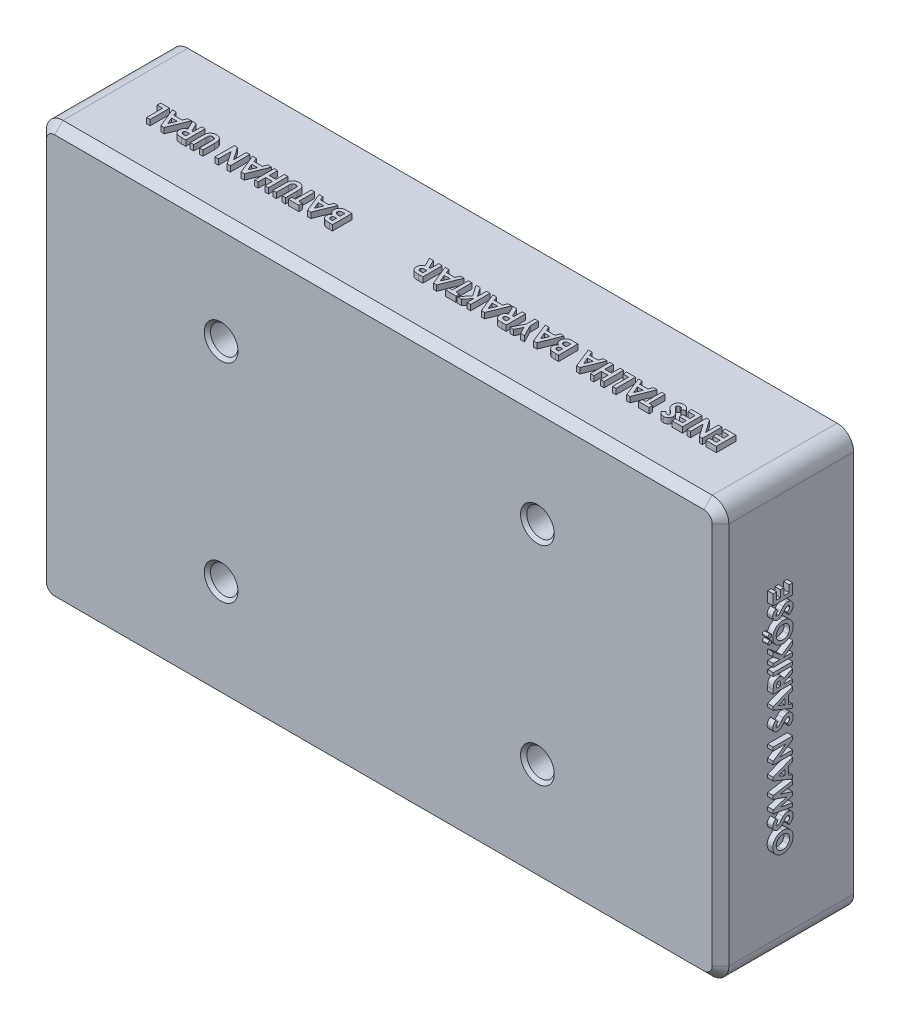
SolidWorks part; units mm, degrees
ref_plane "Ön Düzlem" through (0, 0, 0) normal (0, 0, 1) x (1, 0, 0)
ref_plane "Üst Düzlem" through (0, 0, 0) normal (0, 1, 0) x (1, 0, 0)
ref_plane "Sağ Düzlem" through (0, 0, 0) normal (1, 0, 0) x (0, 0, -1)
sketch "Sketch1" plane through (0, 0, 0) normal (0, 0, 1) x (1, 0, 0)
  line L5 (0, 0) -> (-82, 0)
  line L6 (0, 0) -> (0, 50)
  line L7 (0, 50) -> (-82, 50)
  line L8 (-82, 0) -> (-82, 50)
  dimension "D1" = 82
  dimension "D2" = 50
extrude "Boss-Extrude4" add sketch "Sketch1" along normal blind 16
hole_wizard "M4 Tapped Hole1" positions "Sketch3" profile "Sketch4" tap size "M4" standard "DIN"
sketch "Sketch3" plane through (0, 0, 16) normal (0, 0, 1) x (1, 0, 0)
  line L1 (-41, 50) -> (-41, 0) construction
  line L2 (0, 50) -> (-82, 50) construction
  line L3 (-82, 0) -> (0, 0) construction
  line L6 (-82, 25) -> (0, 25) construction
  line L7 (-82, 50) -> (-82, 0) construction
  line L8 (0, 0) -> (0, 50) construction
  point P0 (-60, 37.5)
  point P2 (-60, 12.5)
  point P4 (-22, 12.5)
  point P6 (-22, 37.5)
  dimension "D1" = 38
  dimension "D2" = 25
sketch "Sketch4" plane through (-60, 37.5, 16) normal (1, 0, 0) x (0, -1, 0)
  line L0 (0, 0) -> (0, 8.9914)
  line L1 (0, 8.9914) -> (1.65, 8)
  line L2 (1.65, 8) -> (1.65, 0.375)
  line L3 (1.65, 0.375) -> (2.025, 0)
  line L5 (2.025, 0) -> (0, 0)
  line L6 (-1.65, 0.375) -> (-2.025, 0) construction
  line L10 (0, 8.9914) -> (-1.65, 8) construction
  line L11 (0, -6.35) -> (0, 107.95) construction
  dimension "Tap Drill Dia." = 3.3
  dimension "Tap Drill Depth" = 8
  dimension "Near C'Sink Dia." = 4.05
  dimension "Near C'Sink Angle" = 90
  dimension "Drill Angle" = 118
cosmetic thread "Hole Thread1" parameters "D1"=6, "D2"=4
cosmetic thread "Hole Thread2" parameters "D1"=6, "D2"=4
cosmetic thread "Hole Thread3" parameters "D1"=6, "D2"=4
cosmetic thread "Hole Thread4" parameters "D1"=6, "D2"=4
scale "Scale1" scale about centroid uniform scaling yes scale factor 1.5
sketch "Sketch5" plane through (0, -12.5, 0) normal (0, -1, 0) x (1, 0, 0)
  line L0 (-102.5, 8.0085) -> (20.5, 8.0085) construction
  line L1 (-102.5, 20.0085) -> (-102.5, -3.9915) construction
  line L2 (20.5, 20.0085) -> (20.5, -3.9915) construction
  text T0 "<b>MUSTAFA USTA                    MUAMMER YAŞIN</b>"
sketch "Sketch6" plane through (0, 62.5, 0) normal (0, 1, 0) x (1, 0, 0)
  line L0 (20.5, -8.0085) -> (-102.5, -8.0085) construction
  text T0 "<b>ENES TALHA BAYRAKTAR          BATUHAN URAL</b>"
sketch "Sketch7" plane through (20.5, 0, 0) normal (1, 0, 0) x (0, 0, -1)
  line L0 (-8.0085, -12.5) -> (-8.0085, 62.5) construction
  line L1 (-20.0085, -12.5) -> (3.9915, -12.5) construction
  line L2 (-20.0085, 62.5) -> (3.9915, 62.5) construction
  text T0 "<b>OSMAN SARIKÖSE</b>"
extrude "Boss-Extrude5" add sketch "Sketch5" along normal blind 1
extrude "Boss-Extrude6" add sketch "Sketch6" along normal blind 1
extrude "Boss-Extrude7" add sketch "Sketch7" along normal blind 1
fillet "Fillet1" radius 3 4 edges at (-102.5, -12.5, 8.0085) (-102.5, 62.5, 8.0085) (20.5, 62.5, 8.0085) (20.5, -12.5, 8.0085)
chamfer "Chamfer1" distance 1.5 angle 45 8 edges at (-41, 62.5, 20.0085) (20.5, 25, 20.0085) (-41, -12.5, 20.0085) (-102.5, 25, 20.0085) (19.6213, 61.6213, 20.0085) (19.6213, -11.6213, 20.0085) (-101.6213, 61.6213, 20.0085) (-101.6213, -11.6213, 20.0085)
